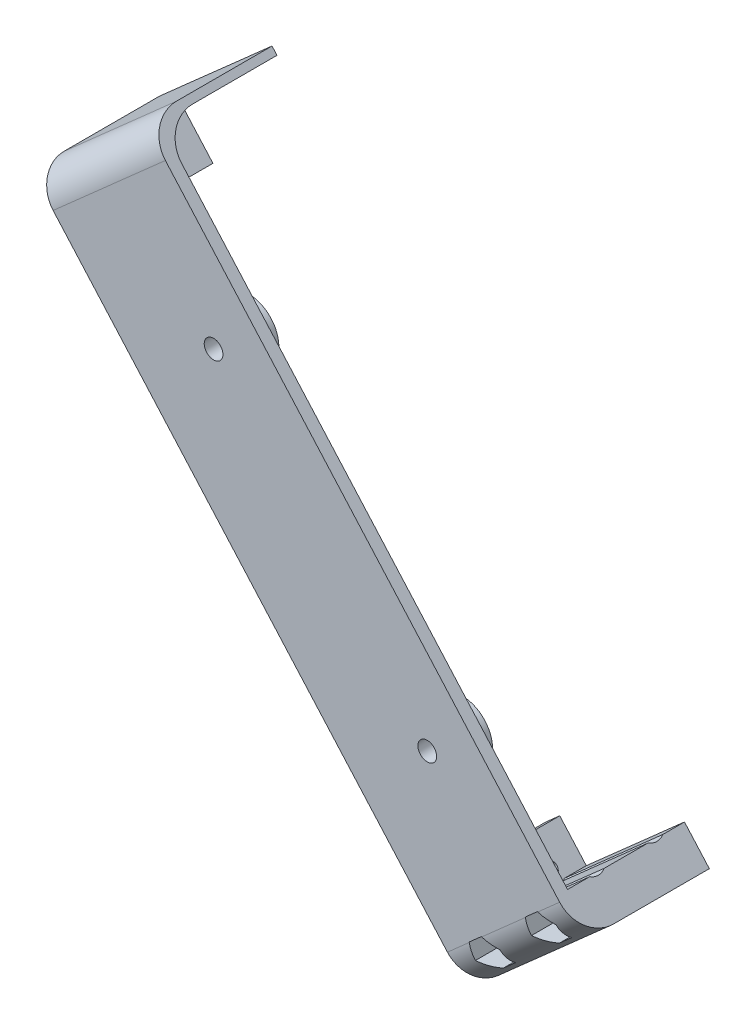
SolidWorks part; units mm, degrees
ref_plane "Front Plane" through (0, 0, 0) normal (0, 0, 1) x (1, 0, 0)
ref_plane "Top Plane" through (0, 0, 0) normal (0, 1, 0) x (1, 0, 0)
ref_plane "Right Plane" through (0, 0, 0) normal (1, 0, 0) x (0, 0, -1)
sketch "Sketch1" plane through (0, 0, 0) normal (0, 0, 1) x (1, 0, 0)
  circle A0 centre (0, 0) radius 10.2489
  circle A1 centre (-72.4111, 81.7658) radius 10.2489
extrude "Boss-Extrude1" add sketch "Sketch1" along normal up to surface (2.9845 mm away)
sketch "Sketch2" plane through (0, 0, 2.9845) normal (0, 0, 1) x (1, 0, 0)
  circle A0 centre (-72.4111, 81.7658) radius 10.2489
  circle A1 centre (0, 0) radius 10.2489
extrude "Boss-Extrude2" add sketch "Sketch2" along normal blind 5.08
sketch "Sketch3" plane through (0, 0, 8.0645) normal (0, 0, 1) x (1, 0, 0)
  line L0 (-134.0697, 103.5005) -> (-96.0391, 137.1801)
  line L1 (-134.0697, 103.5005) -> (14.1204, -63.8342)
  line L2 (-96.0391, 137.1801) -> (52.151, -30.1546)
  line L3 (14.1204, -63.8342) -> (52.151, -30.1546)
  circle A0 centre (0, 0) radius 10.2489 construction
  dimension "D1" = 50.8
  dimension "D2" = 223.52
  dimension "D3" = 19.05
  dimension "D4" = 57.15
extrude "Boss-Extrude3" add sketch "Sketch3" along normal blind 3.81
hole_wizard "1/4 (0.25) Diameter Hole1" positions "Sketch4" profile "Sketch5" hole size "1/4" standard "ANSI Inch" end condition through all
sketch "Sketch4" plane through (0, 0, 11.8745) normal (0, 0, 1) x (1, 0, 0)
  point P0 (0, 0)
  point P3 (-72.4111, 81.7658)
sketch "Sketch5" plane through (0, 0, 11.8745) normal (1, 0, 0) x (0, -1, 0)
  line L0 (0, 0) -> (0, 11.8745)
  line L1 (0, 11.8745) -> (3.175, 11.8745)
  line L2 (3.175, 11.8745) -> (3.175, 0)
  line L5 (3.175, 0) -> (0, 0)
  line L11 (0, -6.35) -> (0, 107.95) construction
  dimension "Thru Hole Dia." = 6.35
  dimension "Thru Hole Depth" = 11.8745
sketch "Sketch7" plane through (0, 0, 8.0645) normal (0, 0, -1) x (-1, 0, 0)
  line L0 (134.0697, 103.5005) -> (129.3159, 107.7104)
  line L1 (134.0697, 103.5005) -> (120.81, 88.5278)
  line L2 (129.3159, 107.7104) -> (116.0562, 92.7378)
  line L3 (120.81, 88.5278) -> (116.0562, 92.7378)
  line L4 (96.0391, 137.1801) -> (134.0697, 103.5005) construction
  line L5 (61.8507, 31.5295) -> (66.6045, 27.3195)
  line L6 (69.7345, 24.5476) -> (46.6379, 45.0017)
  line L7 (61.8507, 31.5295) -> (48.591, 16.5568)
  line L8 (66.6045, 27.3195) -> (53.3448, 12.3468)
  line L9 (48.591, 16.5568) -> (53.3448, 12.3468)
  line L10 (129.3159, 107.7104) -> (96.0391, 137.1801)
  line L11 (134.0697, 103.5005) -> (-14.1204, -63.8342)
  line M7 (-14.1204, -63.8342) -> (134.0697, 103.5005)
  line M8 (134.0697, 103.5005) -> (96.0391, 137.1801)
  dimension "D1" = 20
  dimension "D2" = 6.35
  dimension "D3" = 20
  dimension "D4" = 0
  dimension "D5" = 101.76
  dimension "D6" = 0
  dimension "D7" = 6.35
extrude "Boss-Extrude4" add sketch "Sketch7" along normal blind 17.78 contours L7 L9 L5 M7 | L3 L2 M7 M8 region at (-125.063, 98.1191, 8.0645) region at (-57.5977, 21.9381, 8.0645)
sketch "Sketch8" plane through (-19.0153, -16.8398, 0) normal (0.7486, 0.663, 0) x (0, 0, -1)
  circle A0 centre (0.8255, 54.61) radius 2.25
  circle A1 centre (0.8255, 156.37) radius 2.25
extrude "Cut-Extrude1" cut sketch "Sketch8" against normal blind 17.78
sketch "Sketch9" plane through (-19.0153, -16.8398, 0) normal (0.7486, 0.663, 0) x (0, 0, -1)
  line L0 (9.7155, 64.61) -> (-8.0645, 64.61)
  line L1 (9.7155, 64.61) -> (9.7155, 62.07)
  line L2 (-8.0645, 64.61) -> (-8.0645, 62.07)
  line L3 (9.7155, 62.07) -> (-8.0645, 62.07)
  line L4 (-8.0645, 44.61) -> (9.7155, 44.61)
  line L5 (-8.0645, 44.61) -> (-8.0645, 47.15)
  line L6 (9.7155, 44.61) -> (9.7155, 47.15)
  line L7 (-8.0645, 47.15) -> (9.7155, 47.15)
  line L8 (-8.0645, 166.37) -> (9.7155, 166.37)
  line L9 (-8.0645, 166.37) -> (-8.0645, 163.83)
  line L10 (9.7155, 166.37) -> (9.7155, 163.83)
  line L11 (-8.0645, 163.83) -> (9.7155, 163.83)
  line L12 (9.7155, 146.37) -> (-8.0645, 146.37)
  line L13 (9.7155, 146.37) -> (9.7155, 148.91)
  line L14 (-8.0645, 146.37) -> (-8.0645, 148.91)
  line L15 (9.7155, 148.91) -> (-8.0645, 148.91)
  dimension "D1" = 2.54
extrude "Boss-Extrude5" add sketch "Sketch9" along normal blind 17.78
sketch "Sketch10" plane through (-110.3006, 124.5502, 0) normal (-0.663, 0.7486, 0) x (0.7486, 0.663, 0)
  line L0 (-7.62, 9.7155) -> (-7.62, -8.0645)
  line L1 (-7.62, 9.7155) -> (-25.4, 9.7155)
  line L4 (-25.4, 9.7155) -> (-7.62, -8.0645)
extrude "Cut-Extrude2" cut sketch "Sketch10" against normal up to surface (20 mm away) up to face at (-111.7778, 96.5267, -0.8255)
sketch "Sketch11" plane through (-42.8354, 48.3692, 0) normal (-0.663, 0.7486, 0) x (0.7486, 0.663, 0)
  line L0 (-7.62, 9.7155) -> (-7.62, -8.0645)
  line L1 (-7.62, 9.7155) -> (-25.4, 9.7155)
  line L4 (-25.4, 9.7155) -> (-7.62, -8.0645)
  dimension "D1" = 17.78
extrude "Cut-Extrude3" cut sketch "Sketch11" against normal up to surface (20 mm away) up to face at (-44.3126, 20.3457, -0.8255)
sketch "Sketch13" plane through (-110.3006, 124.5502, 0) normal (-0.663, 0.7486, 0) x (0.7486, 0.663, 0)
  line L0 (-25.4, 9.7155) -> (19.05, 9.7155)
  line L1 (19.05, -8.0645) -> (19.05, 9.7155)
  line L2 (19.05, -8.0645) -> (-7.62, -8.0645)
  line L3 (-7.62, -8.0645) -> (-25.4, 9.7155)
extrude "Boss-Extrude6" add sketch "Sketch13" against normal up to surface (2.54 mm away) up to face at (-123.195, 109.7382, 2.1378)
sketch "Sketch14" plane through (0, 0, 8.0645) normal (0, 0, -1) x (-1, 0, 0)
  line L0 (-52.151, -30.1546) -> (-14.1204, -63.8342)
  line L1 (-52.151, -30.1546) -> (-43.7311, -20.6469)
  line L2 (-14.1204, -63.8342) -> (-5.7005, -54.3265)
  line L3 (-43.7311, -20.6469) -> (-5.7005, -54.3265)
  dimension "D1" = 12.7
extrude "Boss-Extrude7" add sketch "Sketch14" along normal blind 39.624
sketch "Sketch15" plane through (0, 0, 11.8745) normal (0, 0, 1) x (1, 0, 0)
  line L0 (52.151, -30.1546) -> (14.1204, -63.8342)
  line L1 (52.151, -30.1546) -> (43.7311, -20.6469)
  line L2 (14.1204, -63.8342) -> (5.7005, -54.3265)
  line L3 (43.7311, -20.6469) -> (5.7005, -54.3265)
  line L4 (9.9104, -59.0803) -> (47.941, -25.4008)
  line L5 (28.9257, -42.2405) -> (24.7158, -37.4867)
  line L6 (24.7158, -37.4867) -> (52.151, -30.1546)
  line L7 (14.1204, -63.8342) -> (24.7158, -37.4867)
  line L9 (15.3012, -54.3064) -> (20.5171, -56.0488)
  line L10 (20.5171, -56.0488) -> (24.634, -52.4029)
  line L11 (24.634, -52.4029) -> (23.535, -47.0145)
  line L12 (23.535, -47.0145) -> (18.3191, -45.2721)
  line L13 (18.3191, -45.2721) -> (14.2022, -48.918)
  line L14 (14.2022, -48.918) -> (15.3012, -54.3064)
  line L15 (42.5503, -30.1747) -> (37.3344, -28.4323)
  line L16 (37.3344, -28.4323) -> (33.2175, -32.0782)
  line L17 (33.2175, -32.0782) -> (34.3165, -37.4666)
  line L18 (34.3165, -37.4666) -> (39.5324, -39.209)
  line L19 (39.5324, -39.209) -> (43.6493, -35.5631)
  line L20 (43.6493, -35.5631) -> (42.5503, -30.1747)
  circle A0 centre (19.4181, -50.6604) radius 4.7625 construction
  circle A1 centre (38.4334, -33.8207) radius 4.7625 construction
  dimension "D1" = 12.7
  dimension "D2" = 9.525
  dimension "D3" = 9.525
extrude "Cut-Extrude5" cut sketch "Sketch15" against normal blind 6.35 contours L16 L17 L6 L4 L15 | L19 L20 L6 L4 L18 | L6 L20 L4 | L6 L17 L4 | L4 L12 L7 | L4 L9 L7 | L13 L14 L4 L7 L12 | L10 L11 L4 L7 L9 region at (39.5724, -35.9689, 11.8745) region at (41.3421, -32.1947, 11.8745) region at (17.4524, -53.3513, 11.8745) region at (21.4129, -52.0508, 11.8745) region at (37.2944, -31.6724, 11.8745) region at (35.5246, -35.4466, 11.8745) region at (17.4233, -49.27, 11.8745) region at (21.3838, -47.9696, 11.8745)
sketch "Sketch16" plane through (0, 0, 5.5245) normal (0, 0, 1) x (1, 0, 0)
  point P7 (38.4334, -33.8207)
  point P13 (19.4181, -50.6604)
hole_wizard "#6 Clearance Hole1" positions "Sketch17" profile "Sketch18" hole size "#6" standard "ANSI Inch" end condition through all
sketch "Sketch17" plane through (0, 0, 5.5245) normal (0, 0, 1) x (1, 0, 0)
  point P0 (19.4181, -50.6604)
  point P3 (38.4334, -33.8207)
sketch "Sketch18" plane through (19.4181, -50.6604, 5.5245) normal (1, 0, 0) x (0, -1, 0)
  line L0 (0, 0) -> (0, 37.084)
  line L1 (0, 37.084) -> (1.8986, 37.084)
  line L2 (1.8986, 37.084) -> (1.8986, 0)
  line L5 (1.8986, 0) -> (0, 0)
  line L11 (0, -6.35) -> (0, 107.95) construction
  dimension "Thru Hole Dia." = 3.7973
  dimension "Thru Hole Depth" = 37.084
sketch "Sketch19" plane through (-23.7691, -21.0497, 0) normal (-0.7486, -0.663, 0) x (0, 0, 1)
  line L0 (8.0645, -44.45) -> (-31.5595, -44.45)
  line L1 (8.0645, -44.45) -> (8.0645, -30.8895)
  line L2 (-31.5595, -44.45) -> (-31.5595, -30.8895)
  line L3 (8.0645, -30.8895) -> (-31.5595, -30.8895)
extrude "Boss-Extrude8" add sketch "Sketch19" against normal blind 6.35
sketch "Sketch20" plane through (-19.0153, -16.8398, 0) normal (0.7486, 0.663, 0) x (0, 0, -1)
  line L0 (-8.0645, -30.8895) -> (-8.0645, -50.8895)
  line L1 (-8.0645, -30.8895) -> (31.6589, -30.8895)
  line L2 (-8.0645, -50.8895) -> (31.6589, -50.8895)
  line L3 (31.6589, -30.8895) -> (31.6589, -50.8895)
  line L4 (-8.0645, -44.45) -> (-8.0645, -30.8895) construction
  line L6 (11.7972, -30.8895) -> (11.7972, -50.8895)
  line L7 (11.7972, -40.8895) -> (-8.0645, -40.8895)
  line L8 (11.7972, -40.8895) -> (31.6589, -40.8895)
  circle A2 centre (21.728, -40.8895) radius 4.308
  circle A3 centre (1.8663, -40.8895) radius 4.308
  point P12 (1.8663, -40.8895)
  point P13 (21.728, -40.8895)
  line M6 (-8.0645, -44.45) -> (31.5595, -44.45)
  dimension "D1" = 20
hole_wizard "M4 Clearance Hole1" positions "Sketch21" profile "Sketch22" hole size "M4" standard "ANSI Metric" end condition through all
sketch "Sketch21" plane through (-19.0153, -16.8398, 0) normal (0.7486, 0.663, 0) x (0, 0, -1)
  point P0 (1.8663, -40.8895)
  point P3 (21.728, -40.8895)
sketch "Sketch22" plane through (8.0938, -47.4511, -1.8663) normal (0, 0, 1) x (-0.663, 0.7486, 0)
  line L0 (0, 0) -> (0, 117.2901)
  line L1 (0, 117.2901) -> (2.25, 117.2901)
  line L2 (2.25, 117.2901) -> (2.25, 0)
  line L5 (2.25, 0) -> (0, 0)
  line L11 (0, -6.35) -> (0, 107.95) construction
  dimension "Thru Hole Dia." = 4.5
  dimension "Thru Hole Depth" = 117.2901
extrude "Cut-Extrude6" cut sketch "Sketch20" along normal through all contours A3 L7 M6 | L7 A3 M6 | A3 M6 | A2 M6 region at (9.1816, -48.6794, -1.8663) region at (10.6541, -50.3422, -1.8663) region at (10.6541, -50.3422, -21.728)
fillet "Fillet1" radius 11 3 edges at (-110.9935, 120.5437, 8.0645) (-115.0544, 120.3403, 11.8745) (33.1357, -46.9944, 11.8745)
sketch "Sketch23" plane through (0, 0, 5.5245) normal (0, 0, 1) x (1, 0, 0)
  line L0 (37.3344, -28.4323) -> (33.2175, -32.0782) construction
  line L1 (33.2175, -32.0782) -> (34.3165, -37.4666) construction
  line L2 (34.3165, -37.4666) -> (39.5324, -39.209) construction
  line L3 (39.5324, -39.209) -> (43.6493, -35.5631) construction
  line L4 (43.6493, -35.5631) -> (42.5503, -30.1747) construction
  line L5 (42.5503, -30.1747) -> (37.3344, -28.4323) construction
  line L6 (14.2022, -48.918) -> (15.3012, -54.3064) construction
  line L7 (15.3012, -54.3064) -> (20.5171, -56.0488) construction
  line L8 (20.5171, -56.0488) -> (24.634, -52.4029) construction
  line L9 (24.634, -52.4029) -> (23.535, -47.0145) construction
  line L10 (23.535, -47.0145) -> (18.3191, -45.2721) construction
  line L11 (18.3191, -45.2721) -> (14.2022, -48.918) construction
  line L12 (37.3344, -28.4323) -> (33.2175, -32.0782)
  line L13 (33.2175, -32.0782) -> (34.3165, -37.4666)
  line L14 (34.3165, -37.4666) -> (39.5324, -39.209)
  line L15 (39.5324, -39.209) -> (43.6493, -35.5631)
  line L16 (43.6493, -35.5631) -> (42.5503, -30.1747)
  line L17 (42.5503, -30.1747) -> (37.3344, -28.4323)
  line L18 (14.2022, -48.918) -> (15.3012, -54.3064)
  line L19 (15.3012, -54.3064) -> (20.5171, -56.0488)
  line L20 (20.5171, -56.0488) -> (24.634, -52.4029)
  line L21 (24.634, -52.4029) -> (23.535, -47.0145)
  line L22 (23.535, -47.0145) -> (18.3191, -45.2721)
  line L23 (18.3191, -45.2721) -> (14.2022, -48.918)
extrude "Cut-Extrude7" cut sketch "Sketch23" against normal blind 6.35
sketch "Sketch24" plane through (0, 0, -9.7155) normal (0, 0, -1) x (-1, 0, 0)
  line L7 (117.7402, 94.6393) -> (116.0562, 92.7378)
  line L8 (116.0562, 92.7378) -> (120.81, 88.5278)
  line L9 (120.81, 88.5278) -> (134.0697, 103.5005)
  line L10 (134.0697, 103.5005) -> (96.0391, 137.1801)
  line L11 (96.0391, 137.1801) -> (94.3551, 135.2785)
  line L12 (94.3551, 135.2785) -> (127.6319, 105.8089)
  line L13 (127.6319, 105.8089) -> (117.7402, 94.6393)
  line L14 (117.7402, 94.6393) -> (116.0562, 92.7378)
  line L15 (116.0562, 92.7378) -> (120.81, 88.5278)
  line L16 (120.81, 88.5278) -> (134.0697, 103.5005)
  line L17 (134.0697, 103.5005) -> (96.0391, 137.1801)
  line L18 (96.0391, 137.1801) -> (94.3551, 135.2785)
  line L19 (94.3551, 135.2785) -> (127.6319, 105.8089)
  line L20 (127.6319, 105.8089) -> (117.7402, 94.6393)
  dimension "D1" = 0
extrude "Boss-Extrude9" add sketch "Sketch24" along normal up to surface (21.844 mm away) up to face at (21.3167, -50.6604, -31.5595)
